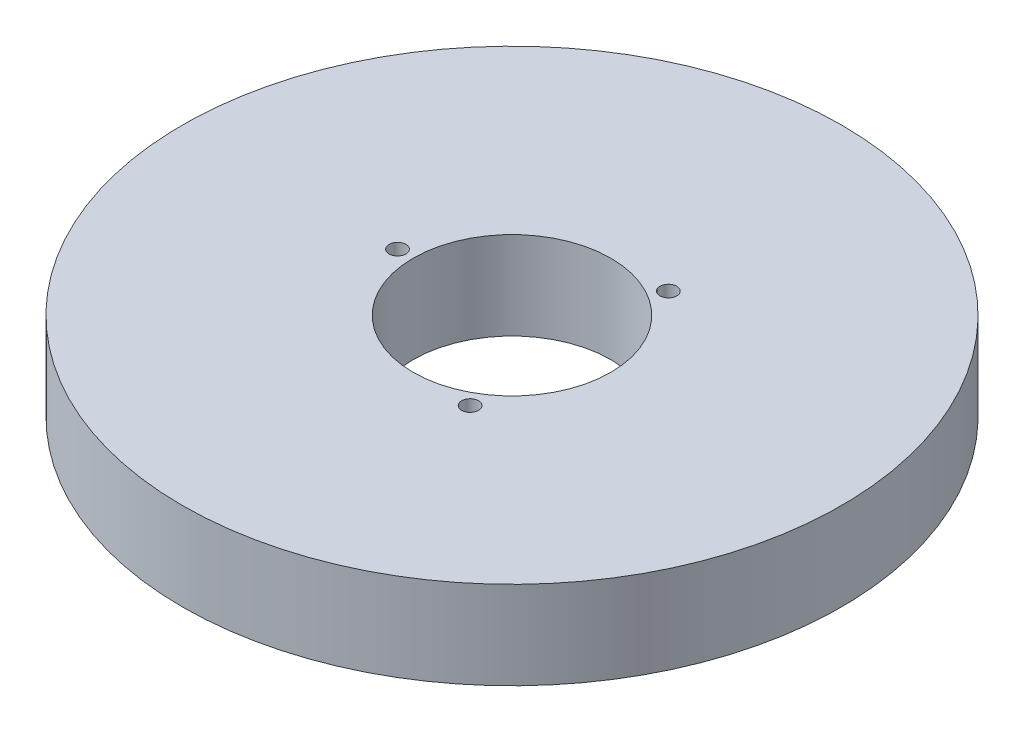
SolidWorks part; units mm, degrees
ref_plane "Front Plane" through (0, 0, 0) normal (0, 0, 1) x (1, 0, 0)
ref_plane "Top Plane" through (0, 0, 0) normal (0, 1, 0) x (1, 0, 0)
ref_plane "Right Plane" through (0, 0, 0) normal (1, 0, 0) x (0, 0, -1)
sketch "Sketch1" plane through (0, 0, 0) normal (0, 1, 0) x (1, 0, 0)
  circle A0 centre (0, 0) radius 75
  dimension "FLANGE_OD" = 150
extrude "Boss-Extrude1" add sketch "Sketch1" along normal blind 20
sketch "Sketch2" plane through (0, 0, 0) normal (0, 1, 0) x (1, 0, 0)
  circle A0 centre (0, 0) radius 22.5
  dimension "BORE_D" = 45
extrude "Cut-Extrude1" cut sketch "Sketch2" along normal through all
sketch "Sketch3" plane through (0, 20, 0) normal (0, 1, 0) x (1, 0, 0)
  circle A0 centre (0, 0) radius 26.0532 construction
  circle A1 centre (-26.0532, 0) radius 1.9092
  dimension "BOLT_D" = 3.8184
  dimension "BOLT_PCD" = 52.1063
extrude "Cut-Extrude2" cut sketch "Sketch3" against normal blind 18.1903
pattern_circular "CirPattern1" count 3 over 360 about axis through (0, 0, 0) along (0, 1, 0) of "Cut-Extrude2"
